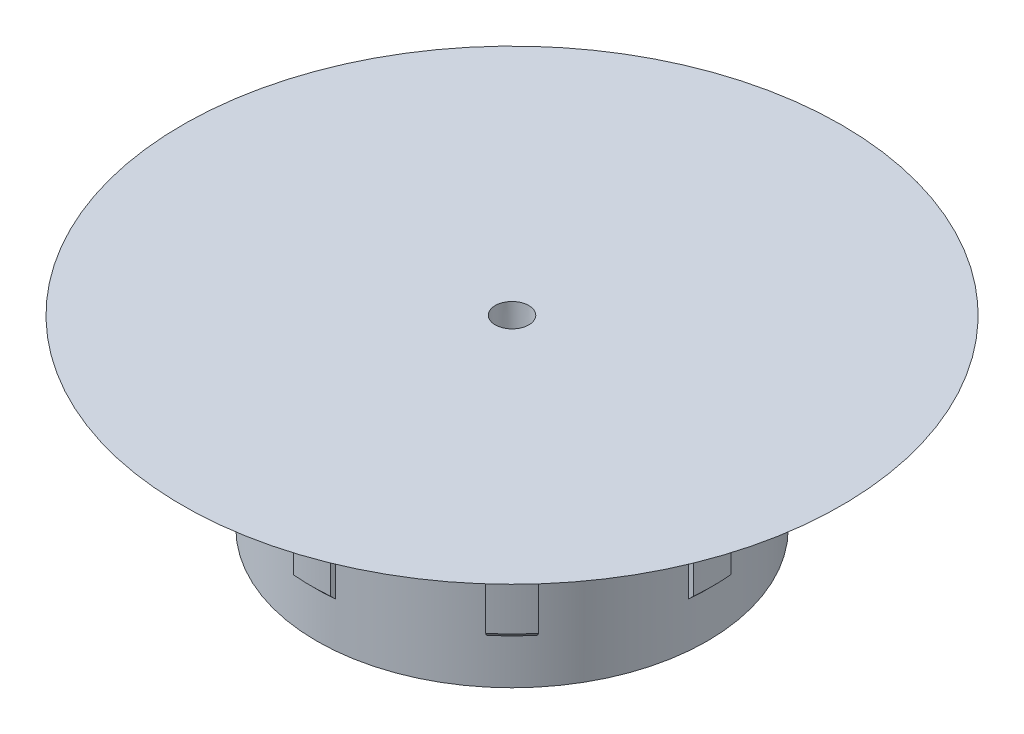
SolidWorks part; units mm, degrees
ref_plane "Front Plane" through (0, 0, 0) normal (0, 0, 1) x (1, 0, 0)
ref_plane "Top Plane" through (0, 0, 0) normal (0, 1, 0) x (1, 0, 0)
ref_plane "Right Plane" through (0, 0, 0) normal (1, 0, 0) x (0, 0, -1)
sketch "Sketch1" plane through (0, 0, 0) normal (0, 0, 1) x (1, 0, 0)
  line L0 (0, 0) -> (0, 23.3158) construction
  line L1 (23.2283, 15.24) -> (38.1, 21.336)
  line L2 (0, 0) -> (23.2283, 0)
  line L3 (0, 0) -> (0, 15.24)
  line L4 (0, 15.24) -> (23.2283, 15.24)
  line L5 (23.2283, 0) -> (23.2283, 15.24)
  line L6 (38.1, 21.336) -> (0, 21.336)
  dimension "D1" = 76.2
  dimension "D2" = 6.096
  dimension "D3" = 15.24
  dimension "D4" = 46.4566
revolve "Revolve1" add sketch "Sketch1" angle 360 about L0 region at (11.6142, 7.62, 0) region at (15.6326, 18.5344, 0)
sketch "Sketch2" plane through (0, 0, 0) normal (0, -1, 0) x (1, 0, 0)
  line L0 (0, 0) -> (0, 23.2283) construction
  line L1 (0, 0) -> (-2.159, 23.1277)
  line L2 (0, 0) -> (2.159, 23.1277)
  line L3 (0, 0) -> (14.8271, 17.8804)
  line L4 (0, 0) -> (17.8804, 14.8271)
  line L5 (0, 0) -> (23.1277, 2.159)
  line L6 (0, 0) -> (23.1277, -2.159)
  line L7 (0, 0) -> (17.8804, -14.8271)
  line L8 (0, 0) -> (14.8271, -17.8804)
  line L9 (0, 0) -> (2.159, -23.1277)
  line L10 (0, 0) -> (-2.159, -23.1277)
  line L11 (0, 0) -> (-14.8271, -17.8804)
  line L12 (0, 0) -> (-17.8804, -14.8271)
  line L13 (0, 0) -> (-23.1277, -2.159)
  line L14 (0, 0) -> (-23.1277, 2.159)
  line L15 (0, 0) -> (-17.8804, 14.8271)
  line L16 (0, 0) -> (-14.8271, 17.8804)
  circle A0 centre (0, 0) radius 22.5806
  circle A2 centre (0, 0) radius 23.2283 construction
  circle A3 centre (0, 0) radius 23.2283 construction
  circle A4 centre (0, 0) radius 23.2283
  circle A6 centre (0, 0) radius 23.2283
  point P29 (0, 0)
  circle M5 centre (0, 0) radius 23.2283
  dimension "D2" = 0.6477
  dimension "D1" = 4.318
  dimension "D3" = 0
  dimension "D4" = 8
extrude "Cut-Extrude1" cut sketch "Sketch2" against normal blind 15.24 contours A0 L3 L2 M5 | A0 L1 L16 M5 | A0 L15 L14 M5 | A0 L13 L12 M5 | A0 L11 L10 M5 | A0 L9 L8 M5 | A0 L7 L6 M5 | A0 L5 L4 M5 region at (-8.6947, 0, 20.9908) region at (2.2679, 0, 22.7923) region at (17.7203, 0, 14.5129) region at (22.7923, 0, -2.2679) region at (14.5129, 0, -17.7203) region at (-2.2679, 0, -22.7923) region at (-17.7203, 0, -14.5129) region at (-22.7923, 0, 2.2679)
sketch "Sketch3" plane through (0, 21.336, 0) normal (0, 1, 0) x (1, 0, 0)
  circle A0 centre (0, 0) radius 1.6764
  dimension "D1" = 3.3528
extrude "Cut-Extrude2" cut sketch "Sketch3" against normal blind 15.24
sketch "Sketch4" plane through (0, 0, 0) normal (0, -1, 0) x (1, 0, 0)
  circle A0 centre (0, 0) radius 22.5806
  circle A1 centre (0, 0) radius 23.2283
extrude "Cut-Extrude3" cut sketch "Sketch4" against normal blind 5.08
chamfer "Chamfer1" distance 0.762 angle 45 8 edges at (0, 5.08, -23.2283) (16.4249, 5.08, -16.4249) (23.2283, 5.08, 0) (16.4249, 5.08, 16.4249) (0, 5.08, 23.2283) (-16.4249, 5.08, 16.4249) (-23.2283, 5.08, 0) (-16.4249, 5.08, -16.4249)
draft "Draft1" type of draft neutral plane draft angle 1 faces to draft 1 face at (0, 6.096, 1.6764) neutral plane through (0, 6.096, 0) neutral plane normal (0, 1, 0) parameters "D1"=1
